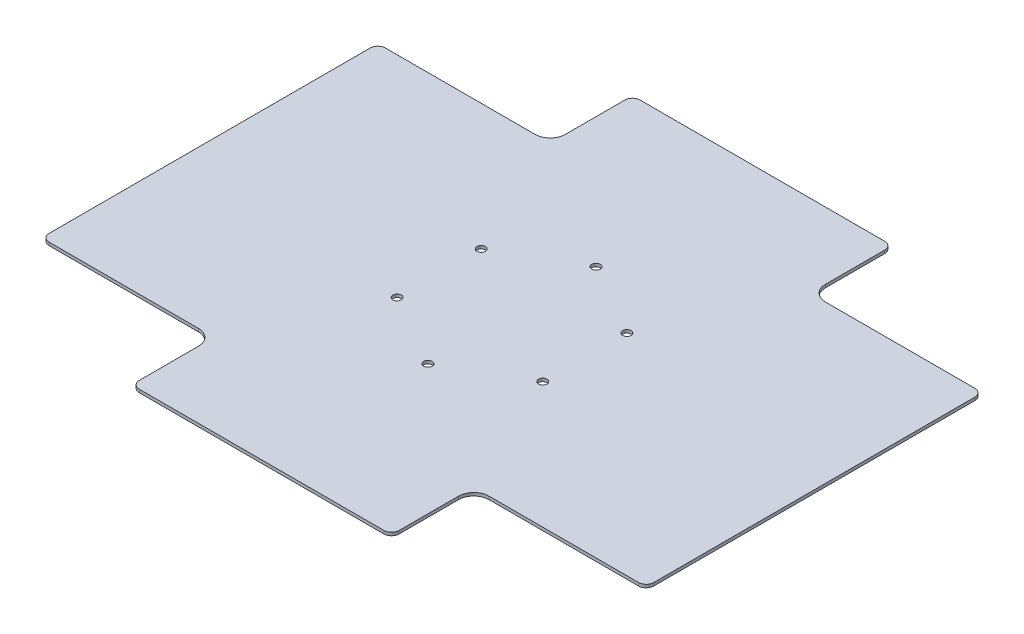
SolidWorks part; units mm, degrees
material "7075-T6, Пластина (SS)"
ref_plane "Спереди" through (0, 0, 0) normal (0, 0, 1) x (1, 0, 0)
ref_plane "Сверху" through (0, 0, 0) normal (0, 1, 0) x (1, 0, 0)
ref_plane "Справа" through (0, 0, 0) normal (1, 0, 0) x (0, 0, -1)
sketch "Эскиз1" plane through (0, 0, 0) normal (0, 1, 0) x (1, 0, 0)
  line L1 (-80, -163.8055) -> (80, -163.8055)
  line L2 (-197.7687, -105) -> (-197.7687, 105)
  line L3 (-80, 163.8055) -> (80, 163.8055)
  line L4 (197.7687, -105) -> (197.7687, 105)
  line L5 (-236.4266, 144.4996) -> (-147.9018, 144.4996) construction
  line L6 (-147.9018, 144.4996) -> (286.4952, 144.4996) construction
  line L18 (-284.5497, 0) -> (284.3305, 0) construction
  line L19 (-160.9018, 110) -> (-134.9018, 110)
  line L20 (-160.9018, 110) -> (-160.9018, 0)
  line L21 (-160.9018, 0) -> (-134.9018, 0)
  line L22 (-134.9018, 110) -> (-134.9018, 0)
  line L23 (-147.9018, -182.6295) -> (-147.9018, 219.9923) construction
  line L24 (-160.9018, 0) -> (-134.9018, 0)
  line L25 (-160.9018, 0) -> (-160.9018, -110)
  line L26 (-160.9018, -110) -> (-134.9018, -110)
  line L27 (-134.9018, 0) -> (-134.9018, -110)
  line L28 (-97.9018, -119.4996) -> (-197.9018, -119.4996)
  line L29 (-97.9018, 169.4996) -> (-197.9018, 169.4996)
  line L30 (-97.9018, 169.4996) -> (-97.9018, 119.4996)
  line L31 (-97.9018, 119.4996) -> (-197.9018, 119.4996)
  line L32 (-197.9018, 169.4996) -> (-197.9018, 119.4996)
  line L33 (-97.9018, 169.4996) -> (-197.9018, 119.4996) construction
  line L34 (-97.9018, 119.4996) -> (-197.9018, 169.4996) construction
  line L35 (-197.9018, -169.4996) -> (-197.9018, -119.4996)
  line L36 (-97.9018, -169.4996) -> (-197.9018, -169.4996)
  line L37 (-97.9018, -169.4996) -> (-97.9018, -119.4996)
  line L39 (-85, 120) -> (-85, 158.8055)
  line L40 (0, 262.7398) -> (0, -186.5795) construction
  line L41 (-192.7687, 110) -> (-95, 110)
  line L43 (-192.7687, -110) -> (-95, -110)
  line L44 (-85, -120) -> (-85, -158.8055)
  line L45 (85, 120) -> (85, 158.8055)
  line L46 (192.7687, 110) -> (95, 110)
  line L47 (192.7687, -110) -> (95, -110)
  line L48 (85, -120) -> (85, -158.8055)
  line L49 (97.9018, -169.4996) -> (97.9018, -119.4996)
  line L50 (97.9018, -169.4996) -> (197.9018, -169.4996)
  line L51 (197.9018, -169.4996) -> (197.9018, -119.4996)
  line L52 (97.9018, -119.4996) -> (197.9018, -119.4996)
  line L53 (160.9018, 0) -> (160.9018, -110)
  line L54 (160.9018, -110) -> (134.9018, -110)
  line L55 (134.9018, 0) -> (134.9018, -110)
  line L56 (160.9018, 0) -> (134.9018, 0)
  line L57 (160.9018, 110) -> (160.9018, 0)
  line L58 (160.9018, 0) -> (134.9018, 0)
  line L59 (134.9018, 110) -> (134.9018, 0)
  line L60 (160.9018, 110) -> (134.9018, 110)
  line L61 (97.9018, 119.4996) -> (197.9018, 119.4996)
  line L62 (197.9018, 169.4996) -> (197.9018, 119.4996)
  line L63 (97.9018, 169.4996) -> (197.9018, 169.4996)
  line L64 (97.9018, 169.4996) -> (97.9018, 119.4996)
  arc A0 (85, -120) -> (95, -110) centre (95, -120) cw
  arc A1 (85, 120) -> (95, 110) centre (95, 120) ccw
  arc A2 (-95, -110) -> (-85, -120) centre (-95, -120) cw
  arc A3 (-85, 120) -> (-95, 110) centre (-95, 120) cw
  arc A4 (192.7687, -110) -> (197.7687, -105) centre (192.7687, -105) ccw
  arc A5 (85, -158.8055) -> (80, -163.8055) centre (80, -158.8055) cw
  arc A6 (-85, -158.8055) -> (-80, -163.8055) centre (-80, -158.8055) ccw
  arc A7 (-192.7687, -110) -> (-197.7687, -105) centre (-192.7687, -105) cw
  arc A8 (-192.7687, 110) -> (-197.7687, 105) centre (-192.7687, 105) ccw
  arc A9 (197.7687, 105) -> (192.7687, 110) centre (192.7687, 105) ccw
  arc A10 (85, 158.8055) -> (80, 163.8055) centre (80, 158.8055) ccw
  arc A11 (-85, 158.8055) -> (-80, 163.8055) centre (-80, 158.8055) cw
  point P0 (0, 0)
  point P3 (85, -110)
  point P17 (-147.9018, 110)
  point P18 (-147.9018, 110)
  point P20 (-147.9018, 0)
  point P22 (-150, 134)
  point P37 (-147.9018, 144.4996)
  point P46 (85, 110)
  point P52 (-85, -110)
  point P55 (-85, 110)
  point P56 (-147.9018, 0)
  point P77 (197.7687, -110)
  point P80 (85, -163.8055)
  point P83 (-85, -163.8055)
  point P86 (-197.7687, -110)
  point P89 (-197.7687, 110)
  point P92 (197.7687, 110)
  point P95 (85, 163.8055)
  point P98 (-85, 163.8055)
  dimension "D2" = 50
  dimension "D6" = 10
  dimension "D4" = 5
  dimension "D3" = 26
  dimension "D5" = 338.9991
  dimension "D7" = 395.5373
  dimension "D8" = 110
  dimension "D9" = 170
  dimension "D10" = 100
  dimension "D13" = 9.4996
  dimension "D14" = 12.9018
sketch "Эскиз2" plane through (0, 0, 0) normal (0, 1, 0) x (1, 0, 0)
  line L0 (-162.9105, 114) -> (-136.9105, 114)
  line L1 (-162.9105, 114) -> (-162.9105, 0)
  line L2 (-162.9105, 0) -> (-136.9105, 0)
  line L3 (-136.9105, 114) -> (-136.9105, 0)
  line L4 (-149.9105, -192.6295) -> (-149.9105, 209.9923) construction
  line L5 (-162.9105, 0) -> (-136.9105, 0)
  line L6 (-162.9105, 0) -> (-162.9105, -114)
  line L7 (-162.9105, -114) -> (-136.9105, -114)
  line L8 (-136.9105, 0) -> (-136.9105, -114)
  line L9 (-99.9105, -123.5568) -> (-199.9105, -123.5568)
  line L10 (-99.9105, 163.4996) -> (-199.9105, 163.4996)
  line L11 (-99.9105, 163.4996) -> (-99.9105, 123.4996)
  line L12 (-99.9105, 123.4996) -> (-199.9105, 123.4996)
  line L13 (-199.9105, 163.4996) -> (-199.9105, 123.4996)
  line L14 (-199.9105, -163.5568) -> (-199.9105, -123.5568)
  line L15 (-99.9105, -163.5568) -> (-199.9105, -163.5568)
  line L16 (-99.9105, -163.5568) -> (-99.9105, -123.5568)
  line L17 (-284.5497, 0) -> (284.3305, 0) construction
  point P11 (-149.9105, 0)
  point P12 (-149.9105, 0)
sketch "Эскиз3" plane through (0, 0, 0) normal (0, 1, 0) x (1, 0, 0)
  line L0 (-89.8176, -177.9027) -> (70.2405, -177.9027)
  line L1 (-209.7886, -106.9112) -> (-209.7886, 106.8353)
  line L2 (-80.029, 172.0973) -> (50.2405, 172.0973)
  line L3 (170.2114, -106.9112) -> (170.2114, 103.9123)
  line L4 (-87.1938, 124.0033) -> (-87.1938, 164.9326)
  line L5 (-202.6239, 114) -> (-97.1971, 114)
  line L6 (-202.6239, -114.076) -> (-106.9857, -114.076)
  line L7 (-96.9823, -124.0793) -> (-96.9823, -170.738)
  line L8 (57.4052, 121.0803) -> (57.4052, 164.9326)
  line L9 (163.0467, 111.077) -> (67.4085, 111.077)
  line L10 (163.0467, -114.076) -> (87.4085, -114.076)
  line L11 (77.4052, -124.0793) -> (77.4052, -170.738)
  line L13 (-162.9105, 114) -> (-136.9105, 114) construction
  arc A0 (77.4052, -124.0793) -> (87.4085, -114.076) centre (87.4085, -124.0793) cw
  arc A1 (57.4052, 121.0803) -> (67.4085, 111.077) centre (67.4085, 121.0803) ccw
  arc A2 (-106.9857, -114.076) -> (-96.9823, -124.0793) centre (-106.9857, -124.0793) cw
  arc A3 (-87.1938, 124.0033) -> (-97.1971, 114) centre (-97.1971, 124.0033) cw
  arc A4 (-80.029, 172.0973) -> (-87.1938, 164.9326) centre (-80.029, 164.9326) ccw
  arc A5 (50.2405, 172.0973) -> (57.4052, 164.9326) centre (50.2405, 164.9326) cw
  arc A6 (170.2114, 103.9123) -> (163.0467, 111.077) centre (163.0467, 103.9123) ccw
  arc A7 (170.2114, -106.9112) -> (163.0467, -114.076) centre (163.0467, -106.9112) cw
  arc A8 (70.2405, -177.9027) -> (77.4052, -170.738) centre (70.2405, -170.738) ccw
  arc A9 (-89.8176, -177.9027) -> (-96.9823, -170.738) centre (-89.8176, -170.738) cw
  arc A10 (-209.7886, -106.9112) -> (-202.6239, -114.076) centre (-202.6239, -106.9112) ccw
  arc A11 (-209.7886, 106.8353) -> (-202.6239, 114) centre (-202.6239, 106.8353) cw
  point P36 (115.2276, 111.077)
  point P39 (-149.9105, 114)
  point P42 (-149.9105, 114)
  dimension "D3" = 10.0033
  dimension "D4" = 7.1647
  dimension "D1" = 380
  dimension "D2" = 350
  dimension "D5" = 112.8062
  dimension "D6" = 63.8267
  dimension "D7" = 61.0203
extrude "Бобышка-Вытянуть1" add sketch "Эскиз1" along normal blind 2 separate body contours A11 L39 A3 L41 L22 L27 L43 A2 L44 A6 L1 A5 L48 A0 L47 L55 L59 L46 A1 L45 A10 L3 | L4 A9 L46 L57 L53 L47 A4 | L46 L59 L56 L57 | L53 L56 L55 L47 | L27 L21 L25 L26 | L41 A8 L2 A7 L43 L25 L20 | L22 L19 L20 L21 region at (0, 0, 0) region at (-147.9018, 0, 55) region at (147.9018, 0, 55) region at (-179.3123, 0, 0) region at (-147.9018, 0, -55) region at (179.3123, 0, 0) region at (147.9018, 0, -55)
sketch "Эскиз4" plane through (0, 2, 0) normal (0, 1, 0) x (1, 0, 0)
  line L0 (197.7687, 0) -> (-197.7687, 0) construction
  line L1 (197.7687, -105) -> (197.7687, 105) construction
  line L2 (-197.7687, -105) -> (-197.7687, 105) construction
  line L3 (197.7687, 0) -> (10, 0) construction
  line L4 (-22, 0) -> (0, 0) construction
  line L5 (0, 0) -> (0, 55) construction
  circle A1 centre (0, 55) radius 2.75
  circle A2 centre (47.6314, 27.5) radius 2.75
  circle A3 centre (47.6314, -27.5) radius 2.75
  circle A4 centre (0, -55) radius 2.75
  circle A5 centre (-47.6314, -27.5) radius 2.75
  circle A6 centre (-47.6314, 27.5) radius 2.75
  circle A7 centre (0, 0) radius 55 construction
  point P14 (0, 0)
  point P17 (0, 0)
  point P18 (0, 0)
  point P29 (0, 0)
  point P31 (0, 0)
  dimension "D1" = 6
  dimension "D2" = 5.5
  dimension "D5" = 55
extrude "Вырез-Вытянуть1" cut sketch "Эскиз4" against normal through all
